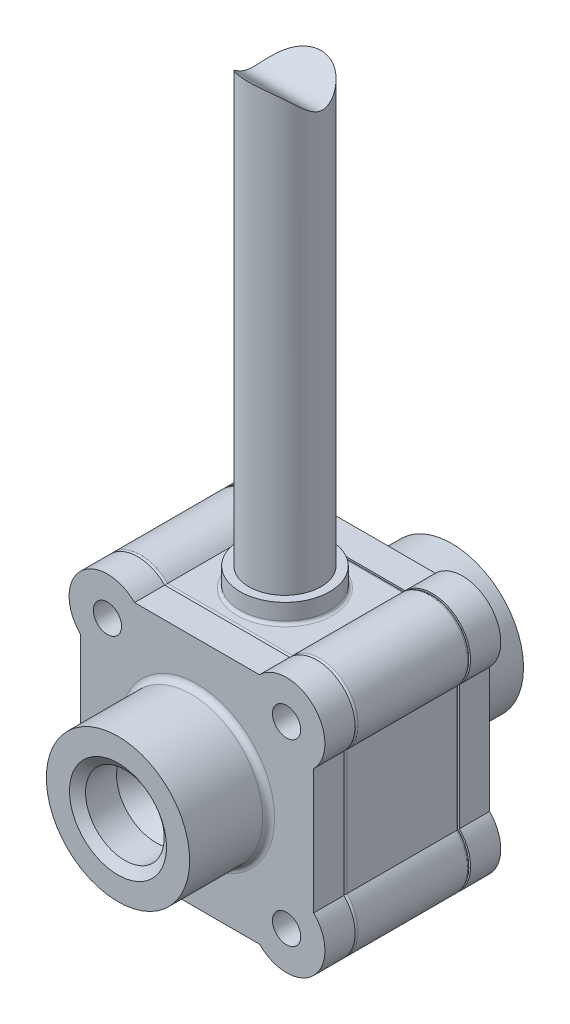
SolidWorks part; units mm, degrees
ref_plane "Front Plane" through (0, 0, 0) normal (0, 0, 1) x (1, 0, 0)
ref_plane "Top Plane" through (0, 0, 0) normal (0, 1, 0) x (1, 0, 0)
ref_plane "Right Plane" through (0, 0, 0) normal (1, 0, 0) x (0, 0, -1)
ref_plane "Plane1" through (0, 0, 35.5) normal (0, 0, 1) x (1, 0, 0)
ref_plane "Plane2" through (0, 0, 18.7) normal (0, 0, 1) x (1, 0, 0)
ref_plane "Plane3" through (0, 0, 12.275) normal (0, 0, 1) x (1, 0, 0)
sketch "Sketch1" plane through (0, 0, 12.275) normal (0, 0, 1) x (1, 0, 0)
  line L0 (0, 27.2) -> (0, -27.2) construction
  line L5 (-24.8129, -24.8129) -> (24.8129, 24.8129) construction
  line L6 (-24.8129, 24.8129) -> (24.8129, -24.8129) construction
  line L7 (-27.2, 0) -> (27.2, 0) construction
  line L8 (-13.2871, -24.8129) -> (13.2871, -24.8129)
  line L9 (24.8129, -13.2871) -> (24.8129, 13.2871)
  line L10 (13.2871, 24.8129) -> (-13.2871, 24.8129)
  line L11 (-24.8129, 13.2871) -> (-24.8129, -13.2871)
  circle A0 centre (-19.05, -19.05) radius 3
  circle A1 centre (19.05, -19.05) radius 3
  circle A2 centre (19.05, 19.05) radius 3
  circle A3 centre (-19.05, 19.05) radius 3
  arc A4 (-24.8129, -13.2871) -> (-13.2871, -24.8129) centre (-19.05, -19.05) ccw
  arc A5 (13.2871, -24.8129) -> (24.8129, -13.2871) centre (19.05, -19.05) ccw
  arc A6 (24.8129, 13.2871) -> (13.2871, 24.8129) centre (19.05, 19.05) ccw
  arc A7 (-13.2871, 24.8129) -> (-24.8129, 13.2871) centre (-19.05, 19.05) ccw
  point P0 (0, 0)
  dimension "D2" = 6
  dimension "D3" = 19.05
extrude "Boss-Extrude1" add sketch "Sketch1" against normal up to surface (12.275 mm away) up to plane "Front Plane"
fillet "Fillet1" radius 0.635 8 edges at (24.8129, -24.8129, 12.275) (0, -24.8129, 12.275) (-24.8129, -24.8129, 12.275) (-24.8129, 0, 12.275) (-24.8129, 24.8129, 12.275) (0, 24.8129, 12.275) (24.8129, 24.8129, 12.275) (24.8129, 0, 12.275)
sketch "Sketch2" plane through (0, 0, 12.275) normal (0, 0, 1) x (1, 0, 0)
  line L4 (-24.8129, 13.2871) -> (-24.8129, -13.2871)
  line L5 (13.2871, 24.8129) -> (-13.2871, 24.8129)
  line L6 (24.8129, -13.2871) -> (24.8129, 13.2871)
  line L7 (-13.2871, -24.8129) -> (13.2871, -24.8129)
  line L8 (-24.8129, 13.2871) -> (-24.8129, -13.2871)
  line L9 (13.2871, 24.8129) -> (-13.2871, 24.8129)
  line L10 (24.8129, -13.2871) -> (24.8129, 13.2871)
  line L11 (-13.2871, -24.8129) -> (13.2871, -24.8129)
  circle A0 centre (-19.05, 19.05) radius 3 construction
  circle A1 centre (-19.05, -19.05) radius 3 construction
  circle A2 centre (19.05, -19.05) radius 3 construction
  circle A3 centre (19.05, 19.05) radius 3 construction
  arc A4 (-24.8129, -13.2871) -> (-13.2871, -24.8129) centre (-19.05, -19.05) ccw
  arc A5 (-13.2871, 24.8129) -> (-24.8129, 13.2871) centre (-19.05, 19.05) ccw
  arc A6 (24.8129, 13.2871) -> (13.2871, 24.8129) centre (19.05, 19.05) ccw
  arc A7 (13.2871, -24.8129) -> (24.8129, -13.2871) centre (19.05, -19.05) ccw
  arc A8 (-24.8129, -13.2871) -> (-13.2871, -24.8129) centre (-19.05, -19.05) ccw
  arc A9 (-13.2871, 24.8129) -> (-24.8129, 13.2871) centre (-19.05, 19.05) ccw
  arc A10 (24.8129, 13.2871) -> (13.2871, 24.8129) centre (19.05, 19.05) ccw
  arc A11 (13.2871, -24.8129) -> (24.8129, -13.2871) centre (19.05, -19.05) ccw
  circle A12 centre (-19.05, 19.05) radius 3
  circle A13 centre (-19.05, -19.05) radius 3
  circle A14 centre (19.05, -19.05) radius 3
  circle A15 centre (19.05, 19.05) radius 3
  dimension "D1" = 0
extrude "Boss-Extrude2" add sketch "Sketch2" along normal up to surface (6.425 mm away) separate body up to plane "Plane2"
sketch "Sketch3" plane through (0, 0, 35.5) normal (0, 0, 1) x (1, 0, 0)
  circle A0 centre (0, 0) radius 15.24
  circle A1 centre (0, 0) radius 5.334
  dimension "D1" = 30.48
  dimension "D2" = 10.668
extrude "Boss-Extrude3" add sketch "Sketch3" against normal up to surface (16.8 mm away) contours A0 up to face at (22.05, 19.05, 18.7)
fillet "Fillet2" radius 1.27 1 edges at (15.24, 0, 18.7)
sketch "Sketch4" plane through (0, 0, 0) normal (1, 0, 0) x (0, 0, -1)
  line L0 (0, 0) -> (-35.5, 0)
  line L1 (-35.5, 29.92) -> (-35.5, -29.92) construction
  line L2 (-35.5, 0) -> (-43.1622, 0)
  line L3 (-43.1622, 0) -> (-43.1622, 10.3177)
  line L4 (-43.1622, 10.3177) -> (-35.5, 10.3177)
  line L5 (-35.5, 10.3177) -> (-34.0406, 8.3672)
  line L6 (-34.0406, 8.3672) -> (-27.4534, 8.3672)
  line L7 (-27.4534, 8.3672) -> (-21.477, 5.334)
  line L8 (-21.477, 5.334) -> (0, 5.334)
  line L9 (0, 29.92) -> (0, -29.92) construction
  line L10 (0, 5.334) -> (0, 0)
  line L11 (-35.5, 15.24) -> (-35.5, -15.24) construction
  dimension "D1" = 5.334
revolve "Cut-Revolve1" cut sketch "Sketch4" angle 360 about L2
mirror "Mirror1" about plane through (0, 0, 0) normal (0, 0, 1) of bodies 104 105
combine bodies "Combine1" operation type add bodies to combine 104 106
sketch "Sketch5" plane through (0, 24.8129, 0) normal (0, 1, 0) x (1, 0, 0)
  circle A0 centre (0, 0) radius 9.525
  dimension "D1" = 19.05
extrude "Boss-Extrude4" add sketch "Sketch5" along normal blind 4.064 contours A0
fillet "Fillet3" radius 0.635 1 edges at (-9.525, 24.8129, 0)
sketch "Sketch6" plane through (0, 28.8769, 0) normal (0, 1, 0) x (1, 0, 0)
  circle A0 centre (0, 0) radius 7.6946
extrude "Boss-Extrude5" add sketch "Sketch6" along normal blind 186.75
sketch "Sketch7" plane through (0, 0, 0) normal (1, 0, 0) x (0, 0, -1)
  line L0 (0, 29.92) -> (0, -29.92) construction
  line L1 (7.6946, 28.8769) -> (7.6946, 215.6269) construction
  spline S0 degree 3 poles (-15.5843, 119.9394) (-8.7386, 127.6563) (-0.8415, 106.703) (10.3564, 125.0843) (16.0819, 119.9394) knots 0 0 0 0 0.500854 1 1 1 1
surface "Surface-Extrude1" sketch "Sketch7" parameters "D1"=21.396, "D2"=18.542
other "SurfaceCut1"
